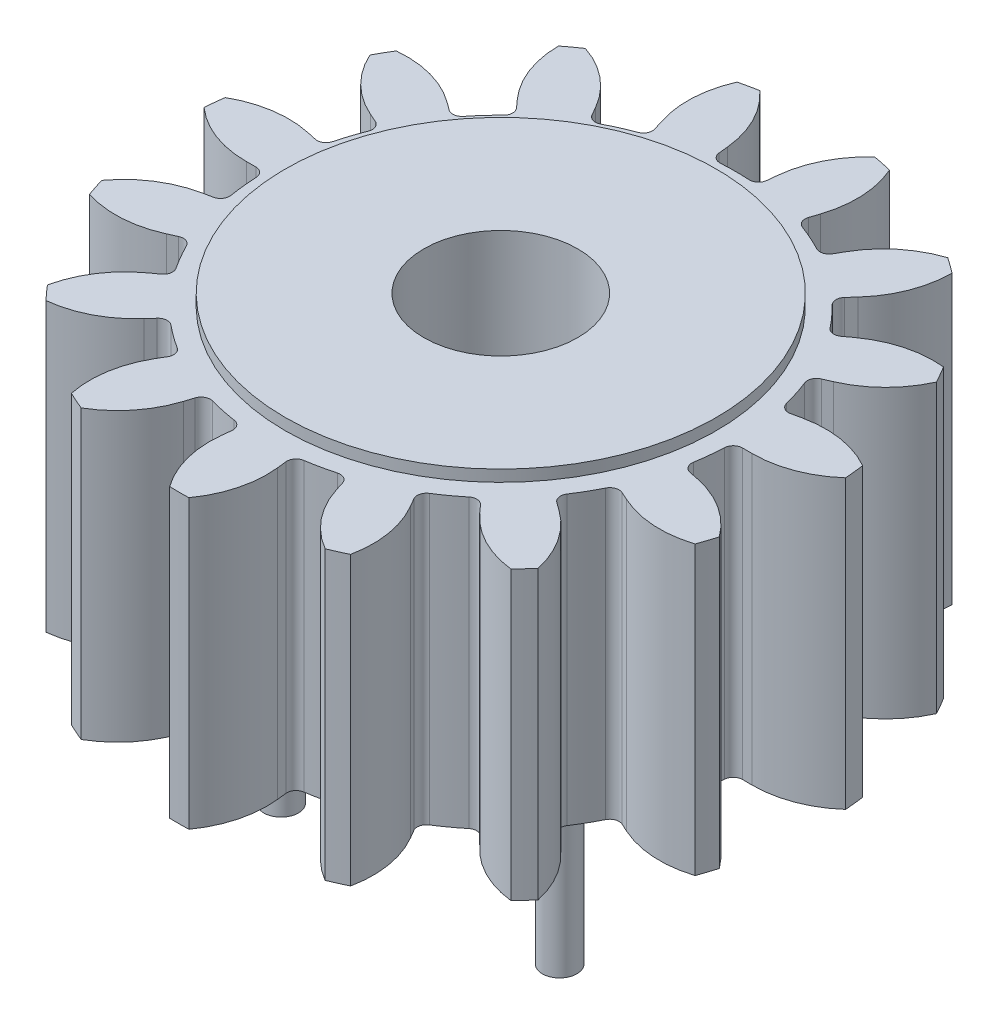
SolidWorks part; units mm, degrees
material "1023 Carbon Steel Sheet (SS)"
ref_plane "Front Plane" through (0, 0, 0) normal (0, 0, 1) x (1, 0, 0)
ref_plane "Top Plane" through (0, 0, 0) normal (0, 1, 0) x (1, 0, 0)
ref_plane "Right Plane" through (0, 0, 0) normal (1, 0, 0) x (0, 0, -1)
sketch "Sketch1" plane through (0, 0, 0) normal (0, 1, 0) x (1, 0, 0)
  circle A0 centre (0, 0) radius 3.556
  dimension "D1" = 7.112
extrude "Boss-Extrude1" add sketch "Sketch1" along normal blind 3.175
ref_axis "Axis1" through (0, 3.175, 0) along (0, -1, 0)
sketch "Sketch2" plane through (0, 3.175, 0) normal (0, 1, 0) x (1, 0, 0)
  circle A0 centre (0, 0) radius 2.3813
  dimension "D1" = 4.7625
extrude "Boss-Extrude2" add sketch "Sketch2" along normal blind 0.127
sketch "Sketch8" plane through (0, 3.175, 0) normal (0, 1, 0) x (1, 0, 0)
  line L0 (0, 0) -> (0, 3.556) construction
  line L1 (0, 0) -> (-0.3486, 3.5389) construction
  line L2 (-0.2739, 2.7805) -> (-0.254, 2.5783)
  line L3 (0.2739, 2.7805) -> (0.254, 2.5783)
  circle A0 centre (0, 0) radius 3.556 construction
  arc A1 (0.635, 3.4988) -> (-0.635, 3.4988) centre (0, 0) ccw
  arc A2 (-0.254, 2.5783) -> (0.254, 2.5783) centre (0, 0) cw
  arc A3 (-0.635, 3.4988) -> (-0.2739, 2.7805) centre (-1.3871, 2.6709) cw
  arc A4 (0.635, 3.4988) -> (0.2739, 2.7805) centre (1.3871, 2.6709) ccw
  dimension "D1" = 0.254
  dimension "D2" = 0.762
  dimension "D3" = 0.2032
  dimension "D4" = 1.27
extrude "Cut-Extrude3" cut sketch "Sketch8" against normal through all
fillet "Fillet1" radius 0.1016 2 edges at (0.254, 1.5875, -2.5783) (-0.254, 1.5875, -2.5783)
pattern_circular "CirPattern3" count 15 over 360 about axis through (0, 3.175, 0) along (0, -1, 0) of "Cut-Extrude3", "Fillet1"
sketch "Sketch5" plane through (0, 0, 0) normal (0, -1, 0) x (1, 0, 0)
  circle A0 centre (0, 0) radius 0.8509
  dimension "D1" = 1.7018
extrude "Cut-Extrude2" cut sketch "Sketch5" against normal up to surface (3.302 mm away) up to face at (0, 3.302, 2.3813)
sketch "Sketch6" plane through (0, 0, 0) normal (0, -1, 0) x (1, 0, 0)
  circle A0 centre (0, -1.778) radius 0.1905
  dimension "D2" = 0.381
  dimension "D1" = 1.778
extrude "Boss-Extrude3" add sketch "Sketch6" along normal blind 1.905
pattern_circular "CirPattern2" count 3 over 360 about axis through (0, 3.175, 0) along (0, -1, 0) of "Boss-Extrude3"
